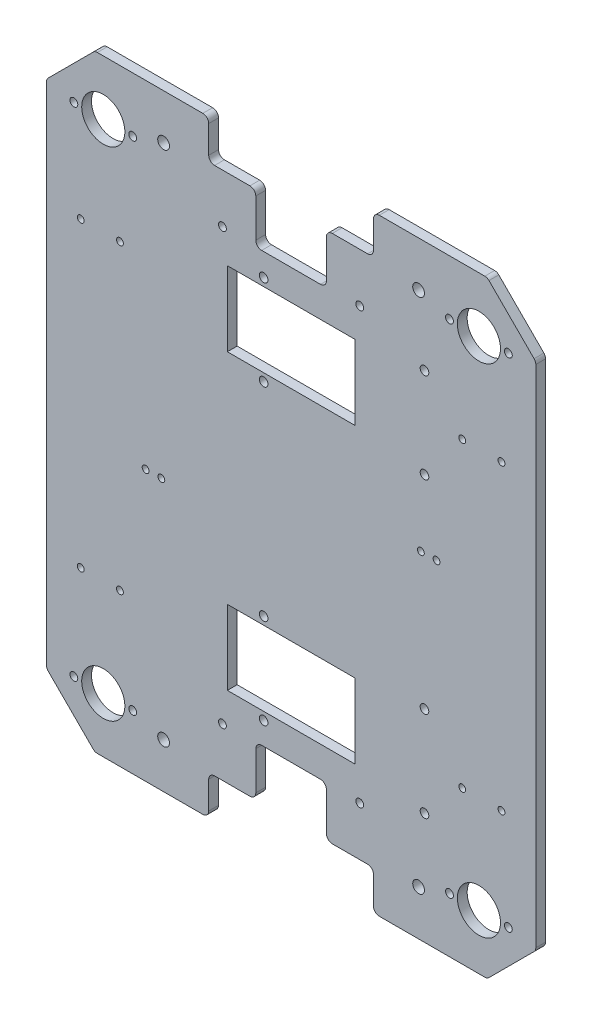
SolidWorks part; units mm, degrees
material "Alliage 1060"
ref_plane "Plan de dessus" through (0, 0, 0) normal (0, 0, 1) x (1, 0, 0)
ref_plane "Plan de droite" through (0, 0, 0) normal (0, 1, 0) x (1, 0, 0)
ref_plane "Plan de face" through (0, 0, 0) normal (1, 0, 0) x (0, 0, -1)
sketch "Esquisse1" plane through (0, 0, 0) normal (0, 0, 1) x (1, 0, 0)
  line L0 (0, 0) -> (-200, 0)
  line L1 (-200, 0) -> (-224.7487, 24.7487)
  line L2 (-224.7487, 24.7487) -> (-224.7487, 284.7487)
  line L3 (-224.7487, 284.7487) -> (-200, 309.4975)
  line L4 (-200, 309.4975) -> (0, 309.4975)
  line L5 (0, 309.4975) -> (24.7487, 284.7487)
  line L6 (24.7487, 284.7487) -> (24.7487, 24.7487)
  line L7 (24.7487, 24.7487) -> (0, 0)
  dimension "D1" = 260
  dimension "D2" = 35
  dimension "D3" = 135
  dimension "D4" = 200
extrude "Base" add sketch "Esquisse1" along normal blind 5
sketch "Esquisse3" plane through (0, 0, 0) normal (0, 0, -1) x (-1, 0, 0)
  line L0 (142, 0) -> (142, 20)
  line L1 (200, 0) -> (0, 0) construction
  line L2 (142, 20) -> (118, 20)
  line L3 (118, 20) -> (118, 45.5)
  line L4 (118, 45.5) -> (82, 45.5)
  line L5 (82, 45.5) -> (82, 20)
  line L6 (82, 20) -> (58, 20)
  line L7 (58, 20) -> (58, 0)
  line L8 (-24.7487, 154.7487) -> (224.7487, 154.7487) construction
  line L9 (-24.7487, 24.7487) -> (-24.7487, 284.7487) construction
  line L10 (224.7487, 284.7487) -> (224.7487, 24.7487) construction
  line L11 (58, 0) -> (142, 0)
  line L12 (58, 309.4975) -> (142, 309.4975)
  line L13 (142, 309.4975) -> (142, 289.4975)
  line L14 (142, 289.4975) -> (118, 289.4975)
  line L15 (118, 289.4975) -> (118, 263.9975)
  line L16 (118, 263.9975) -> (82, 263.9975)
  line L17 (82, 263.9975) -> (82, 289.4975)
  line L18 (82, 289.4975) -> (58, 289.4975)
  line L19 (58, 289.4975) -> (58, 309.4975)
  line L20 (100, 45.5) -> (100, -49954.5) construction
  line L21 (0, 309.4975) -> (200, 309.4975) construction
  line L22 (67.5, 244.4975) -> (132.5, 244.4975)
  line L23 (67.5, 244.4975) -> (67.5, 214.4975)
  line L24 (67.5, 214.4975) -> (132.5, 214.4975)
  line L25 (132.5, 244.4975) -> (132.5, 214.4975)
  line L26 (132.5, 65) -> (132.5, 95)
  line L27 (67.5, 95) -> (132.5, 95)
  line L28 (67.5, 65) -> (132.5, 65)
  line L29 (67.5, 65) -> (67.5, 95)
  circle A0 centre (65, 45) radius 2
  circle A1 centre (135, 45) radius 2
  circle A2 centre (135, 264.4975) radius 2
  circle A3 centre (65, 264.4975) radius 2
  point P4 (100, 45.5)
  point P11 (100, 0)
  point P40 (100, 244.4975)
  point P41 (132.5, 229.4975)
  dimension "D7" = 4
  dimension "D5" = 25
  dimension "D1" = 20
  dimension "D2" = 24
  dimension "D3" = 36
  dimension "D4" = 25.5
  dimension "D6" = 7
  dimension "D8" = 80
  dimension "D9" = 30
  dimension "D10" = 65
extrude "Perçage roues encodeuses" cut sketch "Esquisse3" against normal through all
fillet "Congé1" radius 3 24 edges at (-224.7487, 24.7487, 2.5) (24.7487, 24.7487, 2.5) (0, 0, 2.5) (-142, 20, 2.5) (-118, 45.5, 2.5) (-118, 20, 2.5) (-200, 0, 2.5) (-142, 0, 2.5) (-82, 45.5, 2.5) (-58, 20, 2.5) (-82, 20, 2.5) (-58, 0, 2.5) (24.7487, 284.7487, 2.5) (-142, 289.4975, 2.5) (-118, 263.9975, 2.5) (-224.7487, 284.7487, 2.5) (-200, 309.4975, 2.5) (-142, 309.4975, 2.5) (-118, 289.4975, 2.5) (-82, 263.9975, 2.5) (-58, 289.4975, 2.5) (-82, 289.4975, 2.5) (-58, 309.4975, 2.5) (0, 309.4975, 2.5)
sketch "Esquisse6" plane through (0, 0, 5) normal (0, 0, 1) x (1, 0, 0)
  line L0 (-195.7487, 28) -> (-210.7487, 28) construction
  line L1 (-195.7487, 28) -> (-180.7487, 28) construction
  line L2 (-100, 231.5685) -> (-100, -49768.4315) construction
  line L4 (-67.5, 214.4975) -> (-132.5, 214.4975) construction
  line L5 (-203.2843, 154.7487) -> (49796.7157, 154.7487) construction
  line L6 (-224.7487, 283.5061) -> (-224.7487, 25.9914) construction
  line L15 (-198.7574, 0) -> (-145, 0) construction
  circle A25 centre (-180.7487, 28) radius 2
  circle A26 centre (-210.7487, 28) radius 2
  circle A27 centre (-195.7487, 28) radius 11
  circle A31 centre (-19.2513, 28) radius 2
  circle A32 centre (10.7487, 28) radius 2
  circle A33 centre (-4.2513, 28) radius 11
  circle A34 centre (-4.2513, 281.4975) radius 11
  circle A35 centre (10.7487, 281.4975) radius 2
  circle A36 centre (-19.2513, 281.4975) radius 2
  circle A37 centre (-195.7487, 281.4975) radius 11
  circle A38 centre (-210.7487, 281.4975) radius 2
  circle A39 centre (-180.7487, 281.4975) radius 2
  point P15 (-100, 214.4975)
  point P20 (-224.7487, 154.7487)
  dimension "D2" = 4
  dimension "D3" = 15
  dimension "D4" = 15
  dimension "D5" = 180
  dimension "D9" = 29
  dimension "D13" = 22
  dimension "D15" = 28
extrude "Perçage billes porteuses" cut sketch "Esquisse6" against normal up to next
sketch "Esquisse8" plane through (0, 0, 5) normal (0, 0, 1) x (1, 0, 0)
  line L0 (-100, 263.9975) -> (-100, 95) construction
  line L1 (-85, 263.9975) -> (-115, 263.9975) construction
  line L2 (-132.5, 95) -> (-67.5, 95) construction
  line L3 (-145, 309.4975) -> (-198.7574, 309.4975) construction
  line L4 (-142, 292.4975) -> (-142, 306.4975) construction
  line L5 (-198.7574, 0) -> (-145, 0) construction
  line L6 (-142, 3) -> (-142, 17) construction
  circle A0 centre (-165, 23) radius 3
  circle A1 centre (-165, 286.4975) radius 3
  circle A2 centre (-35, 286.4975) radius 3
  circle A3 centre (-35, 23) radius 3
  dimension "D1" = 23
  dimension "D2" = 23
  dimension "D3" = 6
  dimension "D4" = 23
  dimension "D5" = 23
  dimension "D6" = 6
extrude "Perçage profilés" cut sketch "Esquisse8" against normal up to next
sketch "Esquisse10" plane through (0, 0, 5) normal (0, 0, 1) x (1, 0, 0)
  line L0 (-224.7487, 283.5061) -> (-224.7487, 25.9914) construction
  line L1 (-100, 214.4975) -> (-100, 95) construction
  line L2 (-123.75, 179.6975) -> (-100, 179.6975) construction
  line L3 (-67.5, 214.4975) -> (-132.5, 214.4975) construction
  line L4 (-100, 179.6975) -> (21.8665, 179.6975) construction
  line L5 (-224.7487, 154.7487) -> (24.7487, 154.7487) construction
  line L6 (24.7487, 25.9914) -> (24.7487, 283.5061) construction
  line L7 (-132.5, 95) -> (-67.5, 95) construction
  line L8 (-158.75, 179.6975) -> (-123.75, 179.6975) construction
  line L9 (-132.5, 229.4975) -> (-67.5, 229.4975) construction
  line L10 (-132.5, 214.4975) -> (-132.5, 244.4975) construction
  line L11 (-67.5, 244.4975) -> (-67.5, 214.4975) construction
  line L12 (-100, 129.8) -> (-139.6239, 129.8) construction
  line L13 (-100, 129.8) -> (10.2968, 129.8) construction
  circle A8 centre (-123.75, 179.6975) radius 1.75
  circle A9 centre (-120, 208.4975) radius 1.75
  circle A10 centre (-158.75, 179.6975) radius 1.75
  circle A11 centre (-80, 208.4975) radius 1.75
  circle A18 centre (-80, 101) radius 1.75
  circle A19 centre (-120, 101) radius 1.75
  circle A20 centre (-71.75, 179.6975) radius 1.75
  circle A21 centre (-40.75, 179.6975) radius 1.75
  circle A22 centre (-128.25, 129.8) radius 1.75
  circle A23 centre (-159.25, 129.8) radius 1.75
  circle A24 centre (-76.25, 129.8) radius 1.75
  circle A25 centre (-41.25, 129.8) radius 1.75
  dimension "D1" = 3.5
  dimension "D2" = 23.75
  dimension "D3" = 20
  dimension "D4" = 3.5
  dimension "D5" = 3.5
  dimension "D6" = 35
  dimension "D7" = 21
  dimension "D8" = 28.8
  dimension "D9" = 3.5
  dimension "D10" = 3.5
  dimension "D12" = 31
  dimension "D13" = 28.8
  dimension "D14" = 3.5
  dimension "D15" = 3.5
  dimension "D16" = 3.5
  dimension "D17" = 3.5
  dimension "D18" = 28.25
  dimension "D19" = 31
  dimension "D21" = 35
  dimension "D11" = 28.25
  dimension "D20" = 23.75
sketch "Esquisse15" plane through (0, 0, 0) normal (0, 0, -1) x (-1, 0, 0)
  line L0 (114, 103) -> (32, 103) construction
  line L1 (-24.7487, 154.7487) -> (23.202, 154.7487) construction
  line L2 (-24.7487, 25.9914) -> (-24.7487, 283.5061) construction
  line L3 (100, 95) -> (100, 134.4542) construction
  line L4 (132.5, 95) -> (67.5, 95) construction
  line L5 (0, 80) -> (59.1109, 80) construction
  line L6 (55, 0) -> (1.2426, 0) construction
  circle A0 centre (114, 103) radius 2.2
  circle A1 centre (32, 103) radius 2.2
  circle A2 centre (114, 57) radius 2.2
  circle A3 centre (32, 57) radius 2.2
  circle A4 centre (32, 252.4975) radius 2.2
  circle A5 centre (114, 252.4975) radius 2.2
  circle A6 centre (114, 206.4975) radius 2.2
  circle A7 centre (32, 206.4975) radius 2.2
  dimension "D2" = 4.4
  dimension "D1" = 82
  dimension "D3" = 80
  dimension "D4" = 23
  dimension "D5" = 14
extrude "Perçage bloc moteur" cut sketch "Esquisse15" against normal up to surface (5 mm away) up to face at (-38, 23, 5)
sketch "Esquisse16" plane through (0, 0, 0) normal (0, 0, -1) x (-1, 0, 0)
  line L0 (224.7487, 154.7487) -> (-24.7487, 154.7487) construction
  line L1 (67.5, 61) -> (132.5, 61)
  line L2 (67.5, 61) -> (67.5, 99)
  line L3 (67.5, 99) -> (132.5, 99)
  line L4 (132.5, 61) -> (132.5, 99)
  line L5 (224.7487, 283.5061) -> (224.7487, 25.9914) construction
  line L6 (-24.7487, 25.9914) -> (-24.7487, 283.5061) construction
  line L7 (100, 309.4975) -> (100, 0) construction
  line L8 (100, 0) -> (55, 0) construction
  line L9 (67.5, 210.4975) -> (132.5, 210.4975)
  line L10 (132.5, 248.4975) -> (132.5, 210.4975)
  line L11 (67.5, 248.4975) -> (132.5, 248.4975)
  line L12 (67.5, 248.4975) -> (67.5, 210.4975)
  line L13 (198.7574, 0) -> (145, 0) construction
  point P10 (132.5, 80)
  point P13 (100, 154.7487)
  point P16 (100, 61)
  dimension "D1" = 80
  dimension "D2" = 38
  dimension "D3" = 65
extrude "Enlèv. mat.-Extru.1" cut sketch "Esquisse16" against normal through all
sketch "Esquisse14" plane through (0, 309.4975, 0) normal (0, 1, 0) x (1, 0, 0)
  line L0 (-100, -5) -> (-100, 0) construction
  line L1 (-85, -5) -> (-115, -5) construction
  line L2 (-85, 0) -> (-115, 0) construction
sketch "Esquisse18" plane through (0, 0, 0) normal (0, 0, -1) x (-1, 0, 0)
  line L0 (224.7487, 154.7487) -> (-24.7487, 154.7487) construction
  line L1 (224.7487, 283.5061) -> (224.7487, 25.9914) construction
  line L2 (-24.7487, 25.9914) -> (-24.7487, 283.5061) construction
  line L3 (100, 0) -> (100, 309.4975) construction
  line L4 (197.2487, 231.2487) -> (197.2487, 78.2487) construction
  line L5 (201.2487, 78.2487) -> (193.2487, 78.2487)
  circle A0 centre (201.2487, 78.2487) radius 1.65
  circle A1 centre (193.2487, 78.2487) radius 1.65
  circle A2 centre (193.2487, 231.2487) radius 1.65
  circle A3 centre (201.2487, 231.2487) radius 1.65
  circle A4 centre (-1.2487, 231.2487) radius 1.65
  circle A5 centre (6.7513, 231.2487) radius 1.65
  circle A6 centre (-1.2487, 78.2487) radius 1.65
  circle A7 centre (6.7513, 78.2487) radius 1.65
  point P8 (100, 154.7487)
  point P12 (197.2487, 154.7487)
  point P15 (197.2487, 78.2487)
  dimension "D2" = 3.3
  dimension "D1" = 153
  dimension "D3" = 8
  dimension "D4" = 27.5
sketch "Esquisse17" plane through (0, 0, 0) normal (0, 0, -1) x (-1, 0, 0)
  line L0 (-24.7487, 154.7487) -> (224.7487, 154.7487) construction
  line L1 (-24.7487, 25.9914) -> (-24.7487, 283.5061) construction
  line L2 (224.7487, 283.5061) -> (224.7487, 25.9914) construction
  line L3 (192.7487, 78.2487) -> (192.7487, 231.2487) construction
  line L4 (186.7487, 231.2487) -> (198.7487, 231.2487) construction
  line L5 (100, 309.4975) -> (100, 0) construction
  circle A0 centre (198.7487, 231.2487) radius 2
  circle A1 centre (186.7487, 231.2487) radius 2
  circle A2 centre (198.7487, 78.2487) radius 2
  circle A3 centre (186.7487, 78.2487) radius 2
  circle A4 centre (1.2513, 78.2487) radius 2
  circle A5 centre (13.2513, 78.2487) radius 2
  circle A6 centre (13.2513, 231.2487) radius 2
  circle A7 centre (1.2513, 231.2487) radius 2
  point P9 (192.7487, 154.7487)
  point P12 (192.7487, 231.2487)
  point P21 (100, 154.7487)
  dimension "D3" = 4
  dimension "D1" = 153
  dimension "D2" = 12
  dimension "D4" = 32
sketch "Esquisse19" plane through (0, 0, 0) normal (0, 0, -1) x (-1, 0, 0)
  line L0 (-24.7487, 154.7487) -> (224.7487, 154.7487) construction
  line L1 (-24.7487, 25.9914) -> (-24.7487, 283.5061) construction
  line L2 (224.7487, 283.5061) -> (224.7487, 25.9914) construction
  line L3 (100, 0.2054) -> (100, 309.292) construction
  line L4 (-7.2487, 231.7487) -> (12.7513, 231.7487) construction
  line L5 (25.8513, 171.6987) -> (33.8513, 171.6987) construction
  line L6 (166.1487, 137.7987) -> (174.1487, 137.7987) construction
  circle A0 centre (166.1487, 137.7987) radius 1.75
  circle A1 centre (174.1487, 137.7987) radius 1.75
  circle A8 centre (-7.2487, 231.7487) radius 1.75
  circle A9 centre (12.7513, 231.7487) radius 1.75
  circle A11 centre (12.7513, 77.7487) radius 1.75
  circle A13 centre (-7.2487, 77.7487) radius 1.75
  circle A15 centre (187.2487, 77.7487) radius 1.75
  circle A17 centre (207.2487, 77.7487) radius 1.75
  circle A19 centre (207.2487, 231.7487) radius 1.75
  circle A21 centre (187.2487, 231.7487) radius 1.75
  circle A23 centre (25.8513, 171.6987) radius 1.75
  circle A25 centre (33.8513, 171.6987) radius 1.75
  point P33 (100, 154.7487)
  point P36 (100, 154.7487)
  dimension "D11" = 3.5
  dimension "D9" = 77
  dimension "D10" = 17.5
  dimension "D2" = 20
  dimension "D3" = 16.95
  dimension "D4" = 50.6
  dimension "D5" = 8
  dimension "D6" = 2
extrude "Perçage actionneur Main_De_Dieu" cut sketch "Esquisse19" against normal through all
